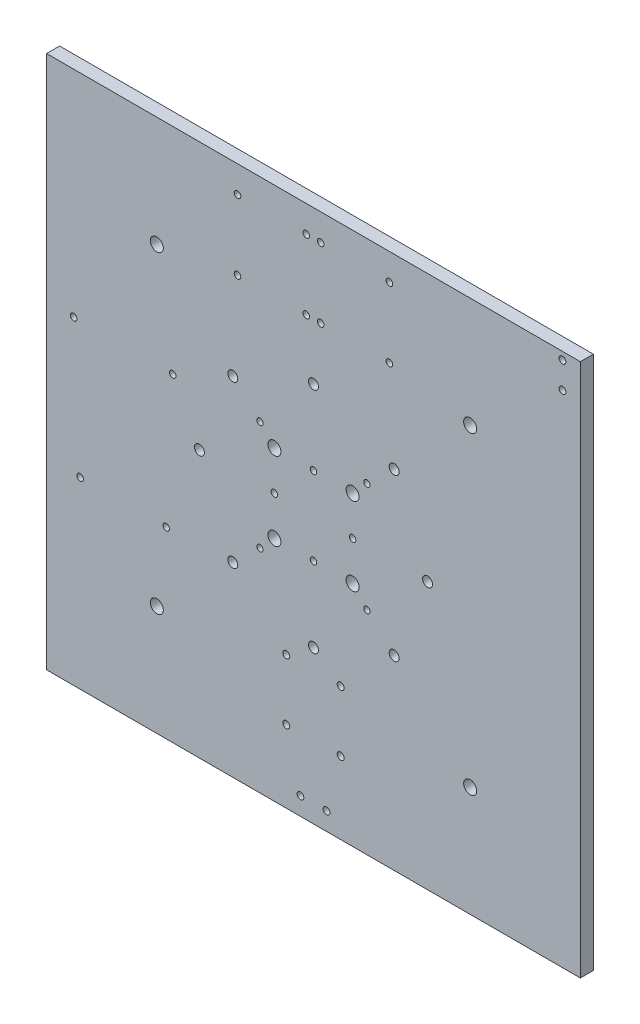
SolidWorks part; units mm, degrees
ref_plane "Front Plane" through (0, 0, 0) normal (0, 0, 1) x (1, 0, 0)
ref_plane "Top Plane" through (0, 0, 0) normal (0, 1, 0) x (1, 0, 0)
ref_plane "Right Plane" through (0, 0, 0) normal (1, 0, 0) x (0, 0, -1)
sketch "Sketch1" plane through (0, 0, 0) normal (0, 0, 1) x (1, 0, 0)
  line L0 (-130, 130) -> (130, 130)
  line L1 (130, 130) -> (130, -130)
  line L2 (130, -130) -> (-130, -130)
  line L3 (-130, -130) -> (-130, 130)
  line L4 (-120, 33.6598) -> (-120, -33.6505)
  line L5 (-29, 8) -> (-29, -8)
  line L6 (-29, 8) -> (-26.035, 8)
  line L7 (-26.035, 8) -> (-26.035, -8)
  line L8 (32.385, 33.02) -> (-32.385, 33.02)
  line L9 (-26.035, -8) -> (-29, -8)
  line L10 (-32.385, 33.02) -> (-32.385, -33.02)
  line L11 (-32.385, -33.02) -> (32.385, -33.02)
  line L12 (32.385, -33.02) -> (32.385, 33.02)
  line L13 (-107.2982, -46.3523) -> (-77.9253, -46.3523)
  line L14 (-113.65, 40.0098) -> (-71.5759, 40.0098)
  line L15 (-79.4148, 40.0098) -> (-79.4148, 22.9992)
  line L16 (-65.2259, -33.6529) -> (-65.2259, 33.6598)
  line L17 (-79.4148, 22.9992) -> (-94.8974, 22.9992)
  line L18 (-40, 120) -> (40, 120)
  line L19 (-94.8974, 22.9992) -> (-94.8974, 40.0098)
  line L31 (-40, 120) -> (-40, 80)
  line L32 (-40, 80) -> (40, 80)
  line L33 (40, 80) -> (40, 120)
  line L34 (-35, 100) -> (-35, 114.5)
  line L35 (-35, 114.5) -> (-29, 114.5)
  line L36 (-29, 114.5) -> (-29, 85.5)
  line L37 (-29, 85.5) -> (-35, 85.5)
  line L38 (-35, 85.5) -> (-35, 100)
  line L46 (16.75, -63) -> (16.75, -97)
  line L49 (16.75, -97) -> (-16.75, -97)
  line L50 (-16.75, -97) -> (-16.75, -63)
  line L51 (-16.75, -63) -> (16.75, -63)
  line L56 (120, 41.2) -> (120, -41.2)
  line L57 (45, 41.2) -> (45, -41.2)
  line L58 (120, 41.2) -> (45, 41.2)
  line L60 (45, -41.2) -> (120, -41.2)
  circle A0 centre (-26.035, 26.67) radius 1.55
  circle A1 centre (-26.035, -26.67) radius 1.55
  circle A2 centre (26.035, 26.67) radius 1.55
  circle A3 centre (26.035, -26.67) radius 1.55
  circle A4 centre (-116.825, 25.4027) radius 1.5875
  circle A5 centre (-113.65, -40.6352) radius 1.5875
  arc A6 (-120, -33.6505) -> (-107.2982, -46.3523) centre (-107.2982, -33.6505) ccw
  arc A7 (-77.9253, -46.3523) -> (-65.2259, -33.6529) centre (-77.9253, -33.6529) ccw
  arc A8 (-113.65, 40.0098) -> (-120, 33.6598) centre (-113.65, 33.6598) ccw
  arc A9 (-65.2259, 33.6598) -> (-71.5759, 40.0098) centre (-71.5759, 33.6598) ccw
  circle A10 centre (-68.565, 25.4048) radius 1.5875
  circle A11 centre (-37, 117) radius 1.6
  circle A12 centre (-37, 83) radius 1.6
  circle A13 centre (-3.5, 117) radius 1.6
  circle A14 centre (-3.5, 83) radius 1.6
  circle A15 centre (3.5, 117) radius 1.6
  circle A16 centre (37, 117) radius 1.6
  circle A17 centre (37, 83) radius 1.6
  circle A18 centre (3.5, 83) radius 1.6
  circle A19 centre (-13.25, -65.25) radius 1.7
  circle A20 centre (13.25, -65.25) radius 1.7
  circle A21 centre (13.25, -94.75) radius 1.7
  circle A22 centre (-13.25, -94.75) radius 1.7
  circle A23 centre (-76.33, 76.33) radius 3.175
  circle A24 centre (0, 55.575) radius 2.415
  circle A25 centre (-55.575, 0) radius 2.415
  circle A26 centre (0, -55.575) radius 2.415
  circle A27 centre (55.575, 0) radius 2.415
  circle A28 centre (-39.2975, 39.2975) radius 2.415
  circle A29 centre (39.2975, 39.2975) radius 2.415
  circle A30 centre (39.2975, -39.2975) radius 2.415
  circle A31 centre (-39.2975, -39.2975) radius 2.415
  circle A32 centre (76.33, 76.33) radius 3.175
  circle A33 centre (76.33, -76.33) radius 3.175
  circle A34 centre (-76.33, -76.33) radius 3.175
  arc A35 (-2.4144, 55.5225) -> (-37.5531, 40.9676) centre (0, 0) ccw
  arc A36 (37.5531, 40.9676) -> (2.4144, 55.5225) centre (0, 0) ccw
  arc A37 (55.5225, 2.4144) -> (40.9676, 37.5531) centre (0, 0) ccw
  arc A38 (40.9676, -37.5531) -> (55.5225, -2.4144) centre (0, 0) ccw
  arc A39 (2.4144, -55.5225) -> (37.5531, -40.9676) centre (0, 0) ccw
  arc A40 (-37.5531, -40.9676) -> (-2.4144, -55.5225) centre (0, 0) ccw
  arc A41 (-55.5225, -2.4144) -> (-40.9676, -37.5531) centre (0, 0) ccw
  arc A42 (-40.9676, 37.5531) -> (-55.5225, 2.4144) centre (0, 0) ccw
  circle A43 centre (-71.74, -40.6352) radius 1.5875
  circle A44 centre (6.35, -121.3) radius 1.651
  circle A45 centre (-6.35, -121.3) radius 1.651
  circle A46 centre (121.3, 126.35) radius 1.651
  circle A47 centre (121.3, 113.65) radius 1.651
  point P127 (127.65, 120)
  point P128 (-120, -120)
  point P129 (0, -127.65)
extrude "Boss-Extrude2" add sketch "Sketch1" along normal blind 6.35 contours L0 L1 L2 L3 | A32 | A33 | A23 | A34 | A10 | A43 | A5 | A4 | A25 | A28 | A24 | A31 | A26 | A30 | A27 | A29 | A1 | A3 | A2 | A0 | A22 | A21 | A20 | A19 | A45 | A44 | A46 | A47 | A17 | A16 | A18 | A14 | A15 | A13 | A11 | A12
sketch "Sketch2" plane through (0, 0, 0) normal (0, 0, -1) x (-1, 0, 0)
  circle A0 centre (0, 19.05) radius 1.5875 construction
  circle A1 centre (-19.05, 0) radius 1.5875 construction
  circle A2 centre (19.05, 0) radius 1.5875 construction
  circle A3 centre (0, -19.05) radius 1.5875 construction
  circle A4 centre (0, 19.05) radius 1.5875
  circle A5 centre (-19.05, 0) radius 1.5875
  circle A6 centre (19.05, 0) radius 1.5875
  circle A7 centre (0, -19.05) radius 1.5875
extrude "Cut-Extrude1" cut sketch "Sketch2" against normal through all contours A5 | A7 | A6 | A4
sketch "Sketch3" plane through (0, 0, 0) normal (0, 0, -1) x (-1, 0, 0)
  circle A0 centre (-19.05, 19.05) radius 3.175 construction
  circle A1 centre (19.05, 19.05) radius 3.175 construction
  circle A2 centre (-19.05, -19.05) radius 3.175 construction
  circle A3 centre (19.05, -19.05) radius 3.175 construction
  circle A4 centre (-19.05, 19.05) radius 3.175
  circle A5 centre (19.05, 19.05) radius 3.175
  circle A6 centre (-19.05, -19.05) radius 3.175
  circle A7 centre (19.05, -19.05) radius 3.175
extrude "Cut-Extrude2" cut sketch "Sketch3" against normal through all contours A6 | A7 | A4 | A5
